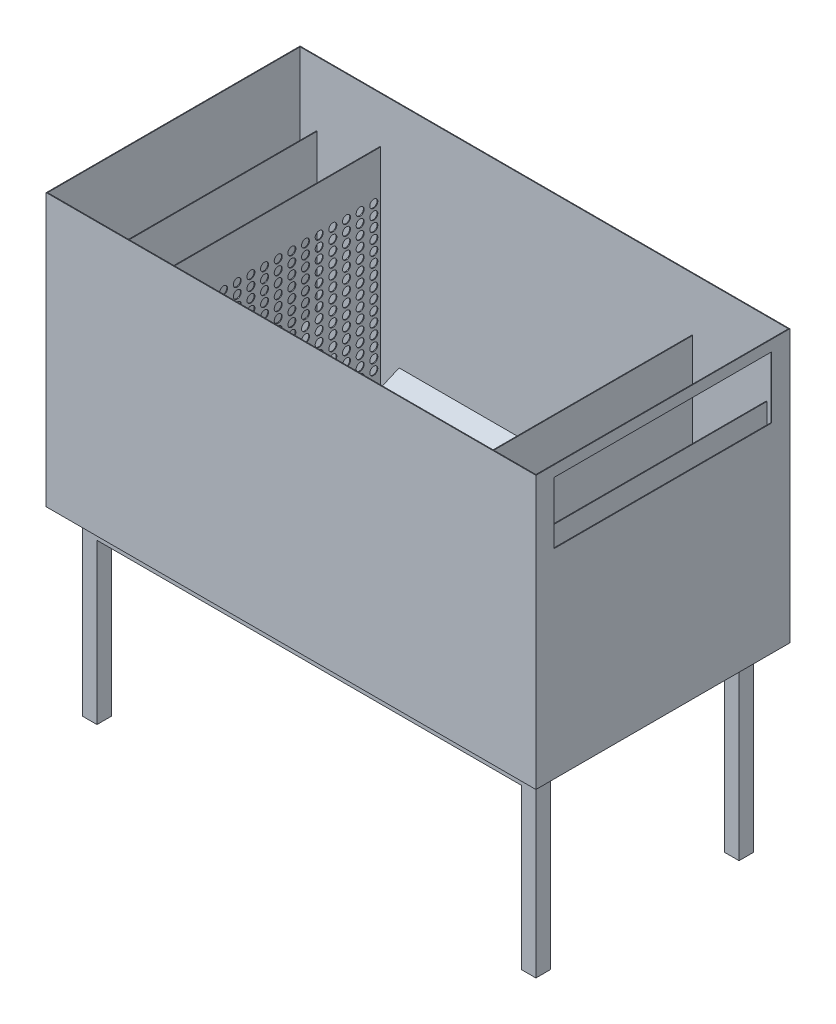
SolidWorks part; units mm, degrees
ref_plane "Спереди" through (0, 0, 0) normal (0, 0, 1) x (1, 0, 0)
ref_plane "Сверху" through (0, 0, 0) normal (0, 1, 0) x (1, 0, 0)
ref_plane "Справа" through (0, 0, 0) normal (1, 0, 0) x (0, 0, -1)
sketch "MASTER_FOOTPRINT" plane through (0, 0, 0) normal (0, 1, 0) x (1, 0, 0)
  line L1 (0, 0) -> (1350, 0)
  line L2 (0, 0) -> (0, 700)
  line L3 (0, 700) -> (1350, 700)
  line L4 (1350, 0) -> (1350, 700)
  dimension "D1" = 1350
  dimension "D2" = 700
extrude "BATH_BASE_PLATE" add sketch "MASTER_FOOTPRINT" along normal blind 750
shell "BATH_SHELL_2MM" thickness 2 removed face at (675, 750, -350)
sketch "Эскиз1" plane through (0, 0, 0) normal (1, 0, 0) x (0, 0, -1)
  circle A0 centre (350, 420) radius 50
extrude "INLET_D100_OPENING" cut sketch "Эскиз1" along normal blind 10
sketch "Эскиз2" plane through (0, 0, 0) normal (1, 0, 0) x (0, 0, -1)
  line L1 (80, 220) -> (620, 220)
  line L2 (80, 220) -> (80, 650)
  line L3 (80, 650) -> (620, 650)
  line L4 (620, 220) -> (620, 650)
extrude "INLET_IMPACT_BAFFLE" add sketch "Эскиз2" along normal blind 2 from offset 125 separate body
sketch "Эскиз3" plane through (0, 0, 0) normal (1, 0, 0) x (0, 0, -1)
  line L1 (30, 2) -> (670, 2)
  line L2 (30, 2) -> (30, 650)
  line L3 (30, 650) -> (670, 650)
  line L4 (670, 2) -> (670, 650)
  circle A0 centre (48.8235, 125) radius 11
  circle A1 centre (48.8235, 153.5) radius 11
  circle A2 centre (48.8235, 182) radius 11
  circle A3 centre (48.8235, 210.5) radius 11
  circle A4 centre (48.8235, 239) radius 11
  circle A5 centre (48.8235, 267.5) radius 11
  circle A6 centre (48.8235, 296) radius 11
  circle A7 centre (48.8235, 324.5) radius 11
  circle A8 centre (48.8235, 353) radius 11
  circle A9 centre (48.8235, 381.5) radius 11
  circle A10 centre (48.8235, 410) radius 11
  circle A11 centre (48.8235, 438.5) radius 11
  circle A12 centre (48.8235, 467) radius 11
  circle A13 centre (48.8235, 495.5) radius 11
  circle A14 centre (48.8235, 524) radius 11
  circle A15 centre (86.4706, 125) radius 11
  circle A16 centre (86.4706, 153.5) radius 11
  circle A17 centre (86.4706, 182) radius 11
  circle A18 centre (86.4706, 210.5) radius 11
  circle A19 centre (86.4706, 239) radius 11
  circle A20 centre (86.4706, 267.5) radius 11
  circle A21 centre (86.4706, 296) radius 11
  circle A22 centre (86.4706, 324.5) radius 11
  circle A23 centre (86.4706, 353) radius 11
  circle A24 centre (86.4706, 381.5) radius 11
  circle A25 centre (86.4706, 410) radius 11
  circle A26 centre (86.4706, 438.5) radius 11
  circle A27 centre (86.4706, 467) radius 11
  circle A28 centre (86.4706, 495.5) radius 11
  circle A29 centre (86.4706, 524) radius 11
  circle A30 centre (124.1176, 125) radius 11
  circle A31 centre (124.1176, 153.5) radius 11
  circle A32 centre (124.1176, 182) radius 11
  circle A33 centre (124.1176, 210.5) radius 11
  circle A34 centre (124.1176, 239) radius 11
  circle A35 centre (124.1176, 267.5) radius 11
  circle A36 centre (124.1176, 296) radius 11
  circle A37 centre (124.1176, 324.5) radius 11
  circle A38 centre (124.1176, 353) radius 11
  circle A39 centre (124.1176, 381.5) radius 11
  circle A40 centre (124.1176, 410) radius 11
  circle A41 centre (124.1176, 438.5) radius 11
  circle A42 centre (124.1176, 467) radius 11
  circle A43 centre (124.1176, 495.5) radius 11
  circle A44 centre (124.1176, 524) radius 11
  circle A45 centre (161.7647, 125) radius 11
  circle A46 centre (161.7647, 153.5) radius 11
  circle A47 centre (161.7647, 182) radius 11
  circle A48 centre (161.7647, 210.5) radius 11
  circle A49 centre (161.7647, 239) radius 11
  circle A50 centre (161.7647, 267.5) radius 11
  circle A51 centre (161.7647, 296) radius 11
  circle A52 centre (161.7647, 324.5) radius 11
  circle A53 centre (161.7647, 353) radius 11
  circle A54 centre (161.7647, 381.5) radius 11
  circle A55 centre (161.7647, 410) radius 11
  circle A56 centre (161.7647, 438.5) radius 11
  circle A57 centre (161.7647, 467) radius 11
  circle A58 centre (161.7647, 495.5) radius 11
  circle A59 centre (161.7647, 524) radius 11
  circle A60 centre (199.4118, 125) radius 11
  circle A61 centre (199.4118, 153.5) radius 11
  circle A62 centre (199.4118, 182) radius 11
  circle A63 centre (199.4118, 210.5) radius 11
  circle A64 centre (199.4118, 239) radius 11
  circle A65 centre (199.4118, 267.5) radius 11
  circle A66 centre (199.4118, 296) radius 11
  circle A67 centre (199.4118, 324.5) radius 11
  circle A68 centre (199.4118, 353) radius 11
  circle A69 centre (199.4118, 381.5) radius 11
  circle A70 centre (199.4118, 410) radius 11
  circle A71 centre (199.4118, 438.5) radius 11
  circle A72 centre (199.4118, 467) radius 11
  circle A73 centre (199.4118, 495.5) radius 11
  circle A74 centre (199.4118, 524) radius 11
  circle A75 centre (237.0588, 125) radius 11
  circle A76 centre (237.0588, 153.5) radius 11
  circle A77 centre (237.0588, 182) radius 11
  circle A78 centre (237.0588, 210.5) radius 11
  circle A79 centre (237.0588, 239) radius 11
  circle A80 centre (237.0588, 267.5) radius 11
  circle A81 centre (237.0588, 296) radius 11
  circle A82 centre (237.0588, 324.5) radius 11
  circle A83 centre (237.0588, 353) radius 11
  circle A84 centre (237.0588, 381.5) radius 11
  circle A85 centre (237.0588, 410) radius 11
  circle A86 centre (237.0588, 438.5) radius 11
  circle A87 centre (237.0588, 467) radius 11
  circle A88 centre (237.0588, 495.5) radius 11
  circle A89 centre (237.0588, 524) radius 11
  circle A90 centre (274.7059, 125) radius 11
  circle A91 centre (274.7059, 153.5) radius 11
  circle A92 centre (274.7059, 182) radius 11
  circle A93 centre (274.7059, 210.5) radius 11
  circle A94 centre (274.7059, 239) radius 11
  circle A95 centre (274.7059, 267.5) radius 11
  circle A96 centre (274.7059, 296) radius 11
  circle A97 centre (274.7059, 324.5) radius 11
  circle A98 centre (274.7059, 353) radius 11
  circle A99 centre (274.7059, 381.5) radius 11
  circle A100 centre (274.7059, 410) radius 11
  circle A101 centre (274.7059, 438.5) radius 11
  circle A102 centre (274.7059, 467) radius 11
  circle A103 centre (274.7059, 495.5) radius 11
  circle A104 centre (274.7059, 524) radius 11
  circle A105 centre (312.3529, 125) radius 11
  circle A106 centre (312.3529, 153.5) radius 11
  circle A107 centre (312.3529, 182) radius 11
  circle A108 centre (312.3529, 210.5) radius 11
  circle A109 centre (312.3529, 239) radius 11
  circle A110 centre (312.3529, 267.5) radius 11
  circle A111 centre (312.3529, 296) radius 11
  circle A112 centre (312.3529, 324.5) radius 11
  circle A113 centre (312.3529, 353) radius 11
  circle A114 centre (312.3529, 381.5) radius 11
  circle A115 centre (312.3529, 410) radius 11
  circle A116 centre (312.3529, 438.5) radius 11
  circle A117 centre (312.3529, 467) radius 11
  circle A118 centre (312.3529, 495.5) radius 11
  circle A119 centre (312.3529, 524) radius 11
  circle A120 centre (350, 125) radius 11
  circle A121 centre (350, 153.5) radius 11
  circle A122 centre (350, 182) radius 11
  circle A123 centre (350, 210.5) radius 11
  circle A124 centre (350, 239) radius 11
  circle A125 centre (350, 267.5) radius 11
  circle A126 centre (350, 296) radius 11
  circle A127 centre (350, 324.5) radius 11
  circle A128 centre (350, 353) radius 11
  circle A129 centre (350, 381.5) radius 11
  circle A130 centre (350, 410) radius 11
  circle A131 centre (350, 438.5) radius 11
  circle A132 centre (350, 467) radius 11
  circle A133 centre (350, 495.5) radius 11
  circle A134 centre (350, 524) radius 11
  circle A135 centre (387.6471, 125) radius 11
  circle A136 centre (387.6471, 153.5) radius 11
  circle A137 centre (387.6471, 182) radius 11
  circle A138 centre (387.6471, 210.5) radius 11
  circle A139 centre (387.6471, 239) radius 11
  circle A140 centre (387.6471, 267.5) radius 11
  circle A141 centre (387.6471, 296) radius 11
  circle A142 centre (387.6471, 324.5) radius 11
  circle A143 centre (387.6471, 353) radius 11
  circle A144 centre (387.6471, 381.5) radius 11
  circle A145 centre (387.6471, 410) radius 11
  circle A146 centre (387.6471, 438.5) radius 11
  circle A147 centre (387.6471, 467) radius 11
  circle A148 centre (387.6471, 495.5) radius 11
  circle A149 centre (387.6471, 524) radius 11
  circle A150 centre (425.2941, 125) radius 11
  circle A151 centre (425.2941, 153.5) radius 11
  circle A152 centre (425.2941, 182) radius 11
  circle A153 centre (425.2941, 210.5) radius 11
  circle A154 centre (425.2941, 239) radius 11
  circle A155 centre (425.2941, 267.5) radius 11
  circle A156 centre (425.2941, 296) radius 11
  circle A157 centre (425.2941, 324.5) radius 11
  circle A158 centre (425.2941, 353) radius 11
  circle A159 centre (425.2941, 381.5) radius 11
  circle A160 centre (425.2941, 410) radius 11
  circle A161 centre (425.2941, 438.5) radius 11
  circle A162 centre (425.2941, 467) radius 11
  circle A163 centre (425.2941, 495.5) radius 11
  circle A164 centre (425.2941, 524) radius 11
  circle A165 centre (462.9412, 125) radius 11
  circle A166 centre (462.9412, 153.5) radius 11
  circle A167 centre (462.9412, 182) radius 11
  circle A168 centre (462.9412, 210.5) radius 11
  circle A169 centre (462.9412, 239) radius 11
  circle A170 centre (462.9412, 267.5) radius 11
  circle A171 centre (462.9412, 296) radius 11
  circle A172 centre (462.9412, 324.5) radius 11
  circle A173 centre (462.9412, 353) radius 11
  circle A174 centre (462.9412, 381.5) radius 11
  circle A175 centre (462.9412, 410) radius 11
  circle A176 centre (462.9412, 438.5) radius 11
  circle A177 centre (462.9412, 467) radius 11
  circle A178 centre (462.9412, 495.5) radius 11
  circle A179 centre (462.9412, 524) radius 11
  circle A180 centre (500.5882, 125) radius 11
  circle A181 centre (500.5882, 153.5) radius 11
  circle A182 centre (500.5882, 182) radius 11
  circle A183 centre (500.5882, 210.5) radius 11
  circle A184 centre (500.5882, 239) radius 11
  circle A185 centre (500.5882, 267.5) radius 11
  circle A186 centre (500.5882, 296) radius 11
  circle A187 centre (500.5882, 324.5) radius 11
  circle A188 centre (500.5882, 353) radius 11
  circle A189 centre (500.5882, 381.5) radius 11
  circle A190 centre (500.5882, 410) radius 11
  circle A191 centre (500.5882, 438.5) radius 11
  circle A192 centre (500.5882, 467) radius 11
  circle A193 centre (500.5882, 495.5) radius 11
  circle A194 centre (500.5882, 524) radius 11
  circle A195 centre (538.2353, 125) radius 11
  circle A196 centre (538.2353, 153.5) radius 11
  circle A197 centre (538.2353, 182) radius 11
  circle A198 centre (538.2353, 210.5) radius 11
  circle A199 centre (538.2353, 239) radius 11
  circle A200 centre (538.2353, 267.5) radius 11
  circle A201 centre (538.2353, 296) radius 11
  circle A202 centre (538.2353, 324.5) radius 11
  circle A203 centre (538.2353, 353) radius 11
  circle A204 centre (538.2353, 381.5) radius 11
  circle A205 centre (538.2353, 410) radius 11
  circle A206 centre (538.2353, 438.5) radius 11
  circle A207 centre (538.2353, 467) radius 11
  circle A208 centre (538.2353, 495.5) radius 11
  circle A209 centre (538.2353, 524) radius 11
  circle A210 centre (575.8824, 125) radius 11
  circle A211 centre (575.8824, 153.5) radius 11
  circle A212 centre (575.8824, 182) radius 11
  circle A213 centre (575.8824, 210.5) radius 11
  circle A214 centre (575.8824, 239) radius 11
  circle A215 centre (575.8824, 267.5) radius 11
  circle A216 centre (575.8824, 296) radius 11
  circle A217 centre (575.8824, 324.5) radius 11
  circle A218 centre (575.8824, 353) radius 11
  circle A219 centre (575.8824, 381.5) radius 11
  circle A220 centre (575.8824, 410) radius 11
  circle A221 centre (575.8824, 438.5) radius 11
  circle A222 centre (575.8824, 467) radius 11
  circle A223 centre (575.8824, 495.5) radius 11
  circle A224 centre (575.8824, 524) radius 11
  circle A225 centre (613.5294, 125) radius 11
  circle A226 centre (613.5294, 153.5) radius 11
  circle A227 centre (613.5294, 182) radius 11
  circle A228 centre (613.5294, 210.5) radius 11
  circle A229 centre (613.5294, 239) radius 11
  circle A230 centre (613.5294, 267.5) radius 11
  circle A231 centre (613.5294, 296) radius 11
  circle A232 centre (613.5294, 324.5) radius 11
  circle A233 centre (613.5294, 353) radius 11
  circle A234 centre (613.5294, 381.5) radius 11
  circle A235 centre (613.5294, 410) radius 11
  circle A236 centre (613.5294, 438.5) radius 11
  circle A237 centre (613.5294, 467) radius 11
  circle A238 centre (613.5294, 495.5) radius 11
  circle A239 centre (613.5294, 524) radius 11
  circle A240 centre (651.1765, 125) radius 11
  circle A241 centre (651.1765, 153.5) radius 11
  circle A242 centre (651.1765, 182) radius 11
  circle A243 centre (651.1765, 210.5) radius 11
  circle A244 centre (651.1765, 239) radius 11
  circle A245 centre (651.1765, 267.5) radius 11
  circle A246 centre (651.1765, 296) radius 11
  circle A247 centre (651.1765, 324.5) radius 11
  circle A248 centre (651.1765, 353) radius 11
  circle A249 centre (651.1765, 381.5) radius 11
  circle A250 centre (651.1765, 410) radius 11
  circle A251 centre (651.1765, 438.5) radius 11
  circle A252 centre (651.1765, 467) radius 11
  circle A253 centre (651.1765, 495.5) radius 11
  circle A254 centre (651.1765, 524) radius 11
extrude "DISTRIBUTOR_D22" add sketch "Эскиз3" along normal blind 2 from offset 250 separate body
sketch "Эскиз4" plane through (0, 0, 0) normal (1, 0, 0) x (0, 0, -1)
  line L1 (50, 320) -> (650, 320)
  line L2 (50, 320) -> (50, 650)
  line L3 (50, 650) -> (650, 650)
  line L4 (650, 320) -> (650, 650)
extrude "OUTLET_SUBMERGED_BAFFLE" add sketch "Эскиз4" along normal blind 2 from offset 1130 separate body
sketch "Эскиз5" plane through (0, 0, 0) normal (1, 0, 0) x (0, 0, -1)
  line L1 (5, 2) -> (695, 2)
  line L2 (5, 2) -> (5, 550)
  line L3 (5, 550) -> (695, 550)
  line L4 (695, 2) -> (695, 550)
extrude "OVERFLOW_WEIR_Z550" add sketch "Эскиз5" along normal blind 2 from offset 1290 separate body
sketch "Эскиз6" plane through (0, 0, 0) normal (1, 0, 0) x (0, 0, -1)
  line L1 (50, 550) -> (650, 550)
  line L2 (50, 550) -> (50, 720)
  line L3 (50, 720) -> (650, 720)
  line L4 (650, 550) -> (650, 720)
extrude "OUTLET_WEIR_SLOT_W600" cut sketch "Эскиз6" along normal blind 10 from offset 1345
sketch "Эскиз7" plane through (0, 0, 0) normal (1, 0, 0) x (0, 0, -1)
  line L0 (2, -1) -> (2, 120)
  line L1 (2, 120) -> (280, -1)
  line L2 (280, -1) -> (2, -1)
  line L3 (698, -1) -> (698, 120)
  line L4 (698, 120) -> (420, -1)
  line L5 (420, -1) -> (698, -1)
extrude "SLOPED_SEDIMENT_FLOOR" add sketch "Эскиз7" along normal blind 825 from offset 275
sketch3d "SCREW_AXIS_30DEG_REFERENCE"
  line L0 (400, 70, -350) -> (1450, 676.2178, -350)
sketch "Эскиз8" plane through (0, 0, 0) normal (0, 1, 0) x (1, 0, 0)
  line L1 (50, 50) -> (90, 50)
  line L2 (50, 50) -> (50, 90)
  line L3 (50, 90) -> (90, 90)
  line L4 (90, 50) -> (90, 90)
  line L6 (50, 610) -> (90, 610)
  line L7 (50, 610) -> (50, 650)
  line L8 (50, 650) -> (90, 650)
  line L9 (90, 610) -> (90, 650)
  line L11 (1260, 50) -> (1300, 50)
  line L12 (1260, 50) -> (1260, 90)
  line L13 (1260, 90) -> (1300, 90)
  line L14 (1300, 50) -> (1300, 90)
  line L16 (1260, 610) -> (1300, 610)
  line L17 (1260, 610) -> (1260, 650)
  line L18 (1260, 650) -> (1300, 650)
  line L19 (1300, 610) -> (1300, 650)
extrude "FRAME_FOUR_LEGS_40X40" add sketch "Эскиз8" against normal blind 500 separate body
sketch "Эскиз9" plane through (0, 0, 0) normal (0, 1, 0) x (1, 0, 0)
  line L1 (50, 50) -> (1300, 50)
  line L2 (50, 50) -> (50, 90)
  line L3 (50, 90) -> (1300, 90)
  line L4 (1300, 50) -> (1300, 90)
  line L6 (50, 610) -> (1300, 610)
  line L7 (50, 610) -> (50, 650)
  line L8 (50, 650) -> (1300, 650)
  line L9 (1300, 610) -> (1300, 650)
extrude "FRAME_LONGITUDINAL_RAILS" add sketch "Эскиз9" against normal blind 40 from offset 20 offset against normal yes
equation "\"AI_Q_Peak\"= 0.006"
equation "\"AI_B_Bath\"= 700"
equation "\"AI_L_Settle\"= 900"
equation "\"AI_L_Inlet\"= 250"
equation "\"AI_L_Outlet\"= 200"
equation "\"AI_L_Bath\"= 1350"
equation "\"AI_H_Water\"= 550"
equation "\"AI_H_Freeboard\"= 200"
equation "\"AI_H_Bath\"= 750"
equation "\"AI_Shell_Thickness\"= 2"
equation "\"AI_Inlet_DN\"= 100"
equation "\"AI_Weir_Width\"= 600"
equation "\"AI_Inlet_Baffle_Offset\"= 125"
equation "\"AI_Distributor_Open_Area\"= 0.28"
equation "\"AI_Distributor_Hole_Dia\"= 22"
equation "\"AI_Distributor_Blind_Zone\"= 110"
equation "\"AI_Outlet_Baffle_Depth\"= 250"
equation "\"AI_Screw_Diameter\"= 100"
equation "\"AI_Screw_Pitch\"= 100"
equation "\"AI_Screw_Angle\"= 30"
equation "\"AI_Screw_Rpm\"= 15"
equation "\"AI_Screw_Clearance\"= 5"
equation "\"AI_Liner_Thickness\"= 5"
equation "\"AI_Discharge_Height\"= 650"
equation "\"AI_Frame_Height\"= 500"
equation "\"D1@MASTER_FOOTPRINT\" = \"AI_L_Bath\""
equation "\"D2@MASTER_FOOTPRINT\" = \"AI_B_Bath\""
equation "\"D1@BATH_BASE_PLATE\" = \"AI_H_Bath\""
